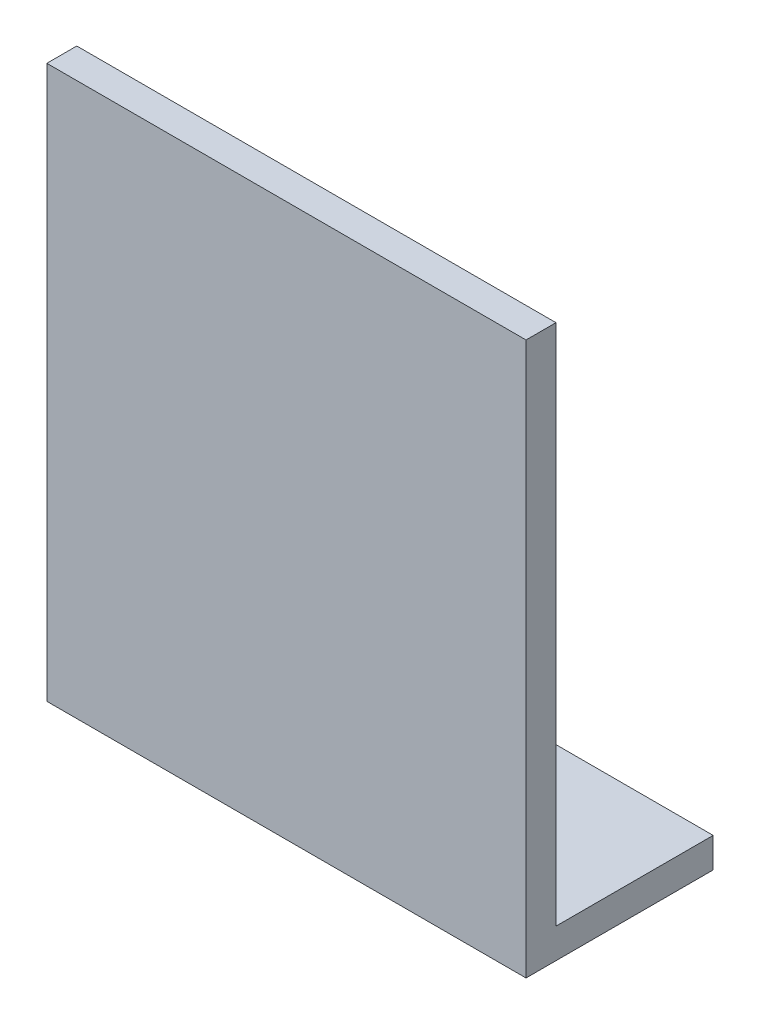
SolidWorks part; units mm, degrees
ref_plane "Front Plane" through (0, 0, 0) normal (0, 0, 1) x (1, 0, 0)
ref_plane "Top Plane" through (0, 0, 0) normal (0, 1, 0) x (1, 0, 0)
ref_plane "Right Plane" through (0, 0, 0) normal (1, 0, 0) x (0, 0, -1)
sketch "Sketch1" plane through (0, 0, 0) normal (0, 1, 0) x (1, 0, 0)
  line L1 (0, 0) -> (32.0076, 0)
  line L2 (0, 0) -> (0, 12.5)
  line L3 (0, 12.5) -> (32.0076, 12.5)
  line L4 (32.0076, 0) -> (32.0076, 12.5)
  dimension "D1" = 12.5
extrude "Boss-Extrude1" add sketch "Sketch1" along normal blind 2
sketch "Sketch2" plane through (0, 0, 0) normal (0, 0, 1) x (1, 0, 0)
  line L1 (0, 2) -> (32.0076, 2)
  line L2 (0, 2) -> (0, 36.9085)
  line L3 (0, 36.9085) -> (32.0076, 36.9085)
  line L4 (32.0076, 2) -> (32.0076, 36.9085)
extrude "Boss-Extrude2" add sketch "Sketch2" against normal blind 2
